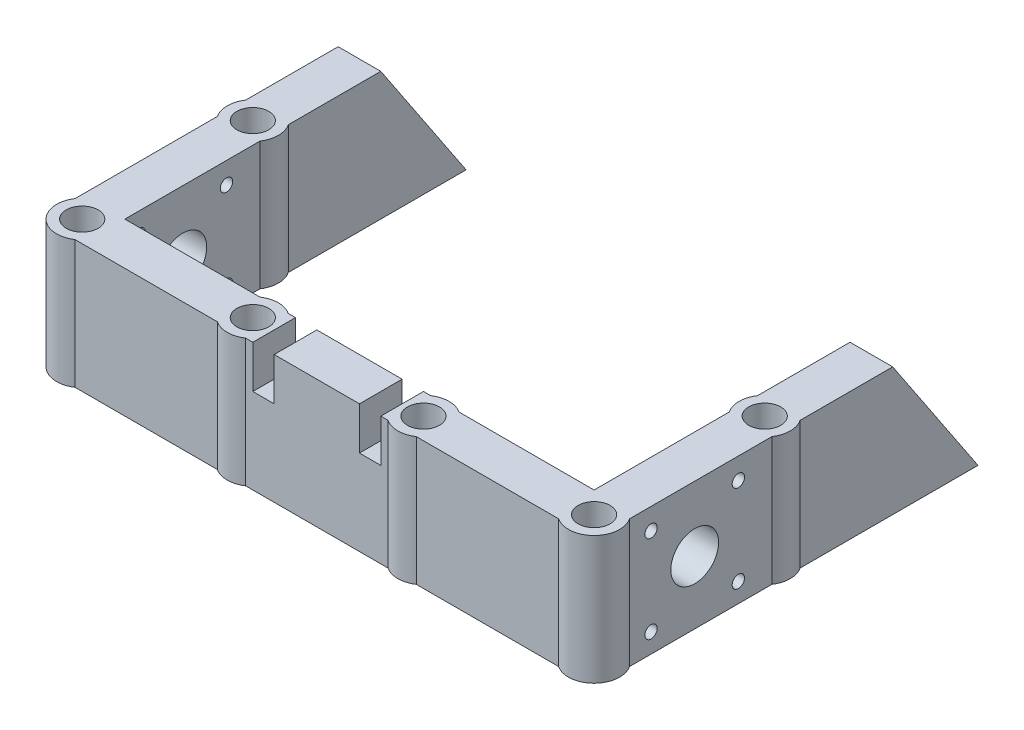
SolidWorks part; units mm, degrees
material "Custom Plastic"
ref_plane "Front Plane" through (0, 0, 0) normal (0, 0, 1) x (1, 0, 0)
ref_plane "Top Plane" through (0, 0, 0) normal (0, 1, 0) x (1, 0, 0)
ref_plane "Right Plane" through (0, 0, 0) normal (1, 0, 0) x (0, 0, -1)
sketch "Sketch4" plane through (0, 0, 0) normal (0, 1, 0) x (1, 0, 0)
  line L0 (0, 0) -> (0, -52.9379)
  line L1 (0, -114.3) -> (52.9379, -114.3) construction
  line L2 (165.1, -103.7379) -> (165.1, -61.3621)
  line L3 (165.1, 0) -> (152.4, 0)
  line L4 (152.4, 0) -> (152.4, -52.9379)
  line L5 (152.4, -101.6) -> (112.1621, -101.6)
  line L6 (12.7, -101.6) -> (12.7, -61.3621)
  line L7 (12.7, 0) -> (0, 0)
  line L8 (6.35, -107.95) -> (57.15, -107.95) construction
  line L9 (57.15, -107.95) -> (107.95, -107.95) construction
  line L10 (107.95, -107.95) -> (158.75, -107.95) construction
  line L11 (158.75, -107.95) -> (158.75, -57.15) construction
  line L12 (6.35, -107.95) -> (6.35, -57.15) construction
  line L13 (12.7, -52.9379) -> (12.7, 0)
  line L14 (0, -61.3621) -> (0, -114.3) construction
  line L15 (0, -61.3621) -> (0, -103.7379)
  line L16 (10.5621, -114.3) -> (52.9379, -114.3)
  line L17 (52.9379, -101.6) -> (12.7, -101.6)
  line L18 (61.3621, -114.3) -> (103.7379, -114.3) construction
  line L19 (61.3621, -114.3) -> (103.7379, -114.3)
  line L20 (103.7379, -101.6) -> (61.3621, -101.6)
  line L21 (112.1621, -114.3) -> (165.1, -114.3) construction
  line L22 (112.1621, -114.3) -> (154.5379, -114.3)
  line L23 (152.4, -61.3621) -> (152.4, -101.6)
  line L24 (165.1, -52.9379) -> (165.1, 0)
  circle A0 centre (6.35, -107.95) radius 4.7625
  circle A1 centre (6.35, -57.15) radius 4.7625
  circle A2 centre (57.15, -107.95) radius 4.7625
  circle A3 centre (107.95, -107.95) radius 4.7625
  circle A4 centre (158.75, -107.95) radius 4.7625
  circle A5 centre (158.75, -57.15) radius 4.7625
  arc A6 (0, -52.9379) -> (0, -61.3621) centre (6.35, -57.15) ccw
  arc A7 (12.7, -61.3621) -> (12.7, -52.9379) centre (6.35, -57.15) ccw
  arc A8 (0, -103.7379) -> (10.5621, -114.3) centre (6.35, -107.95) ccw
  arc A9 (61.3621, -101.6) -> (52.9379, -101.6) centre (57.15, -107.95) ccw
  arc A10 (52.9379, -114.3) -> (61.3621, -114.3) centre (57.15, -107.95) ccw
  arc A11 (103.7379, -114.3) -> (112.1621, -114.3) centre (107.95, -107.95) ccw
  arc A12 (112.1621, -101.6) -> (103.7379, -101.6) centre (107.95, -107.95) ccw
  arc A13 (154.5379, -114.3) -> (165.1, -103.7379) centre (158.75, -107.95) ccw
  arc A14 (152.4, -52.9379) -> (152.4, -61.3621) centre (158.75, -57.15) ccw
  arc A15 (165.1, -61.3621) -> (165.1, -52.9379) centre (158.75, -57.15) ccw
  point P30 (158.75, 0)
  dimension "D6" = 9.525
  dimension "D8" = 7.62
  dimension "D10" = 15.24
  dimension "D11" = 7.62
  dimension "D12" = 7.62
  dimension "D13" = 15.24
  dimension "D14" = 15.24
  dimension "D1" = 12.7
  dimension "D2" = 12.7
  dimension "D3" = 12.7
  dimension "D4" = 165.1
  dimension "D5" = 114.3
  dimension "D7" = 6.35
  dimension "D9" = 50.8
extrude "Boss-Extrude2" add sketch "Sketch4" along normal blind 38.1
chamfer "Chamfer2" distance 38.1 distance2 25.4 2 edges at (158.75, 38.1, 0) (6.35, 38.1, 0) first distance on face at (158.75, 19.05, 0) first distance on face at (6.35, 19.05, 0)
sketch "Sketch6" plane through (0, 0, 114.3) normal (0, 0, 1) x (1, 0, 0)
  line L0 (63.5, 38.1) -> (63.5, 25.4)
  line L1 (61.3621, 38.1) -> (103.7379, 38.1) construction
  line L2 (63.5, 25.4) -> (69.85, 25.4)
  line L3 (69.85, 25.4) -> (69.85, 38.1)
  line L4 (95.25, 38.1) -> (95.25, 25.4)
  line L5 (95.25, 25.4) -> (101.6, 25.4)
  line L6 (101.6, 25.4) -> (101.6, 38.1)
  line L7 (95.25, 38.1) -> (101.6, 38.1)
  line L8 (63.5, 38.1) -> (69.85, 38.1)
  line L9 (61.3621, 38.1) -> (63.5, 38.1) construction
  line L10 (101.6, 38.1) -> (103.7379, 38.1) construction
  dimension "D1" = 6.35
  dimension "D2" = 6.35
  dimension "D3" = 12.7
  dimension "D4" = 12.7
  dimension "D5" = 25.4
extrude "Cut-Extrude3" cut sketch "Sketch6" against normal through all
sketch "Sketch7" plane through (165.1, 0, 0) normal (1, 0, 0) x (0, 0, -1)
  line L0 (-71.3409, 31.7589) -> (-97.3409, 5.7589) construction
  line L1 (-71.3409, 31.7589) -> (-71.3409, 5.7589) construction
  line L2 (-71.3409, 5.7589) -> (-97.3409, 5.7589) construction
  line L3 (-97.3409, 5.7589) -> (-97.3409, 31.7589) construction
  line L4 (-97.3409, 31.7589) -> (-71.3409, 31.7589) construction
  circle A0 centre (-84.3409, 18.7589) radius 7.112
  circle A1 centre (-71.3409, 31.7589) radius 1.8415
  circle A2 centre (-71.3409, 5.7589) radius 1.8415
  circle A3 centre (-97.3409, 5.7589) radius 1.8415
  circle A4 centre (-97.3409, 31.7589) radius 1.8415
  point P10 (-84.3409, 18.7589)
  dimension "D2" = 14.224
  dimension "D3" = 3.683
  dimension "D1" = 26
extrude "Cut-Extrude4" cut sketch "Sketch7" against normal through all
